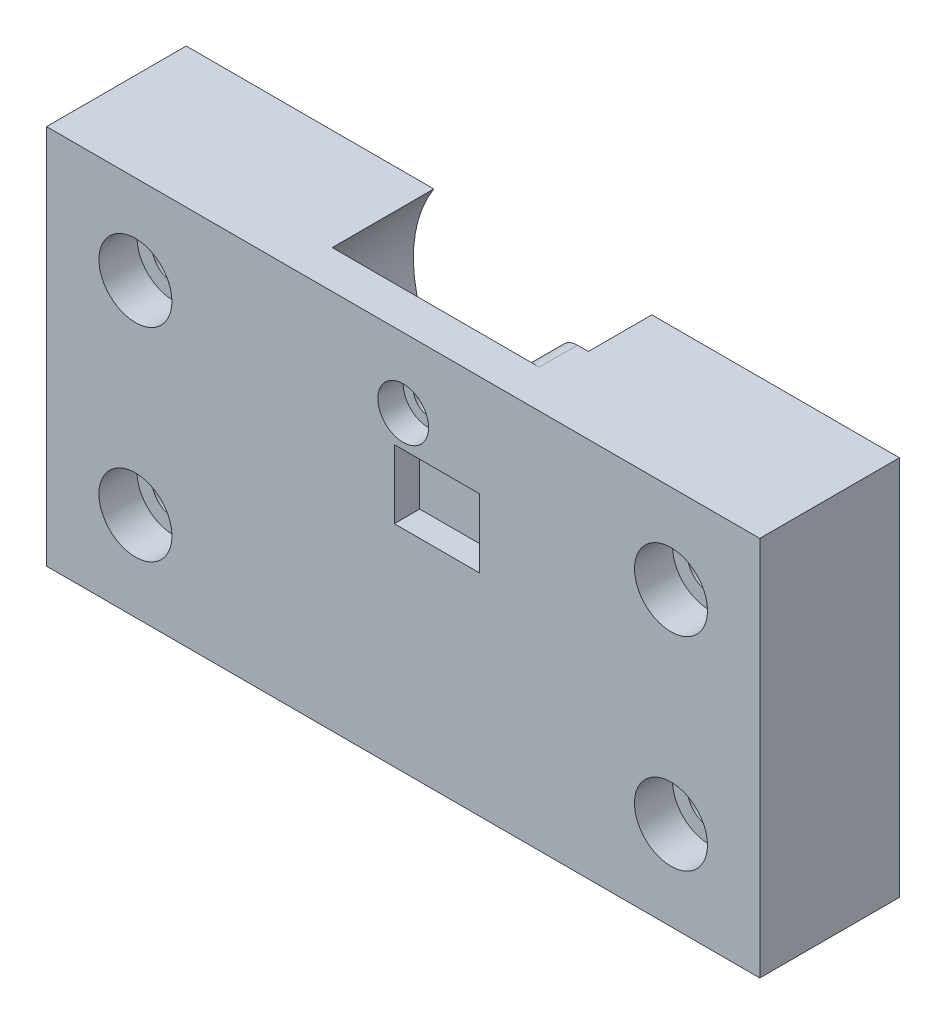
SolidWorks part; units mm, degrees
ref_plane "Front Plane" through (0, 0, 0) normal (0, 0, 1) x (1, 0, 0)
ref_plane "Top Plane" through (0, 0, 0) normal (0, 1, 0) x (1, 0, 0)
ref_plane "Right Plane" through (0, 0, 0) normal (1, 0, 0) x (0, 0, -1)
sketch "Sketch1" plane through (0, 0, 0) normal (0, 0, 1) x (1, 0, 0)
  line L0 (19.5099, 0) -> (0, 0)
  line L1 (28.1, -5.5) -> (28.1, -10) construction
  line L2 (0, 0) -> (0, -30)
  line L3 (0, -30) -> (56.2, -30)
  line L4 (36.6901, 0) -> (56.2, 0)
  line L5 (56.2, 0) -> (56.2, -30)
  line L6 (19.5099, 0) -> (36.6901, 0) construction
  line L7 (35.8259, 0) -> (36.6901, 0)
  line L8 (35.8259, -3) -> (37.9889, -3)
  line L18 (0, -15) -> (56.2, -15) construction
  arc A0 (19.5099, 0) -> (37.9889, -3) centre (28.1, -5.5) ccw
  arc A1 (35.8259, 0) -> (35.8259, -3) centre (35.8259, -1.5) ccw
  dimension "D4" = 30
  dimension "D5" = 1.5
  dimension "D2" = 5.5
  dimension "D1" = 10.2
  dimension "D3" = 56.2
extrude "Boss-Extrude1" add sketch "Sketch1" along normal blind 8
sketch "Sketch2" [suppressed] plane through (0, 0, 0) normal (0, 0, -1) x (-1, 0, 0)
  line L0 (-56.2, -15) -> (0, -15) construction
  line L1 (-56.2, -30) -> (-56.2, 0) construction
  line L2 (-46.0015, -7) -> (-47.6007, -4.23)
  line L3 (-47.6007, -4.23) -> (-50.7993, -4.23)
  line L4 (-50.7993, -4.23) -> (-52.3985, -7)
  line L5 (-52.3985, -7) -> (-50.7993, -9.77)
  line L6 (-50.7993, -9.77) -> (-47.6007, -9.77)
  line L7 (-47.6007, -9.77) -> (-46.0015, -7)
  line L8 (0, 0) -> (0, -30) construction
  line L9 (-8.5993, -9.77) -> (-10.1985, -7)
  line L10 (-28.1, 0) -> (-28.1, -30) construction
  line L11 (0, -30) -> (-56.2, -30) construction
  line L12 (-5.4007, -9.77) -> (-8.5993, -9.77)
  line L13 (-3.8015, -7) -> (-5.4007, -9.77)
  line L14 (-5.4007, -4.23) -> (-3.8015, -7)
  line L15 (-8.5993, -4.23) -> (-5.4007, -4.23)
  line L16 (-10.1985, -7) -> (-8.5993, -4.23)
  line L17 (-10.1985, -23) -> (-8.5993, -25.77)
  line L18 (-8.5993, -25.77) -> (-5.4007, -25.77)
  line L19 (-5.4007, -25.77) -> (-3.8015, -23)
  line L20 (-3.8015, -23) -> (-5.4007, -20.23)
  line L21 (-5.4007, -20.23) -> (-8.5993, -20.23)
  line L22 (-8.5993, -20.23) -> (-10.1985, -23)
  line L23 (-47.6007, -20.23) -> (-46.0015, -23)
  line L24 (-50.7993, -20.23) -> (-47.6007, -20.23)
  line L25 (-52.3985, -23) -> (-50.7993, -20.23)
  line L26 (-50.7993, -25.77) -> (-52.3985, -23)
  line L27 (-47.6007, -25.77) -> (-50.7993, -25.77)
  line L28 (-46.0015, -23) -> (-47.6007, -25.77)
  circle A0 centre (-49.2, -7) radius 2.77 construction
  circle A1 centre (-7, -7) radius 2.77 construction
  circle A2 centre (-7, -23) radius 2.77 construction
  circle A3 centre (-49.2, -23) radius 2.77 construction
  dimension "D1" = 5.54
  dimension "D2" = 7
  dimension "D3" = 7
extrude "Cut-Extrude1" [suppressed] cut sketch "Sketch2" against normal blind 2.4
sketch "Sketch3" plane through (0, 0, 8) normal (0, 0, 1) x (1, 0, 0)
  line L0 (0, 0) -> (0, -30)
  line L1 (0, -30) -> (56.2, -30)
  line L2 (56.2, -30) -> (56.2, 0) construction
  line L3 (56.2, -30) -> (56.2, 0)
  line L4 (0, 0) -> (56.2, 0)
extrude "Boss-Extrude2" add sketch "Sketch3" along normal blind 3
sketch "Sketch4" plane through (0, 0, 0) normal (0, 0, -1) x (-1, 0, 0)
  line L0 (-56.2, -15) -> (0, -15) construction
  line L1 (-56.2, -30) -> (-56.2, 0) construction
  line L2 (0, 0) -> (0, -30) construction
  line L3 (-28.1, -5.5) -> (-28.1, -30) construction
  line L8 (0, -30) -> (-56.2, -30) construction
  circle A0 centre (-49.2, -7) radius 1.7
  circle A1 centre (-7, -7) radius 1.7
  circle A2 centre (-7, -23) radius 1.7
  circle A3 centre (-49.2, -23) radius 1.7
  circle A4 centre (-28.1, -5.5) radius 1.2
  arc A5 (-37.9889, -3) -> (-19.5099, 0) centre (-28.1, -5.5) ccw construction
  dimension "D1" = 3.4
  dimension "D4" = 2.4
  dimension "D2" = 7
  dimension "D3" = 7
extrude "Cut-Extrude2" cut sketch "Sketch4" against normal up to surface (11 mm away) up to face at (28.1, -15, 11)
sketch "Sketch5" plane through (0, 0, 0) normal (0, 0, -1) x (-1, 0, 0)
  line L0 (-19.5099, 0) -> (-36.6901, 0)
  line L1 (-56.2, 0) -> (-35.8259, 0) construction
  arc A0 (-36.6901, 0) -> (-19.5099, 0) centre (-28.1, -5.5) ccw
extrude "Cut-Extrude3" cut sketch "Sketch5" against normal blind 5
sketch "Sketch7" plane through (0, 0, 11) normal (0, 0, 1) x (1, 0, 0)
  line L0 (28.1, -5.5) -> (28.1, -30) construction
  line L1 (27.4, -8) -> (34.1, -8)
  line L2 (27.4, -8) -> (27.4, -13.4)
  line L3 (27.4, -13.4) -> (34.1, -13.4)
  line L4 (34.1, -8) -> (34.1, -13.4)
  line L5 (0, -30) -> (56.2, -30) construction
  circle A0 centre (28.1, -5.5) radius 2
  dimension "D1" = 4
  dimension "D2" = 6.7
  dimension "D3" = 5.4
  dimension "D4" = 8
  dimension "D5" = 27.4
extrude "Cut-Extrude4" cut sketch "Sketch7" against normal blind 2
sketch "Sketch8" plane through (0, 0, 11) normal (0, 0, 1) x (1, 0, 0)
  line L0 (28.1, 0) -> (28.1, -30) construction
  line L1 (56.2, 0) -> (0, 0) construction
  line L2 (0, -30) -> (56.2, -30) construction
  line L3 (0, -15) -> (56.2, -15) construction
  line L4 (0, 0) -> (0, -30) construction
  line L5 (56.2, -30) -> (56.2, 0) construction
  circle A0 centre (7, -7) radius 2.875
  circle A1 centre (49.2, -7) radius 2.875
  circle A2 centre (49.2, -23) radius 2.875
  circle A3 centre (7, -23) radius 2.875
  dimension "D1" = 5.75
extrude "Cut-Extrude5" cut sketch "Sketch8" against normal blind 3
